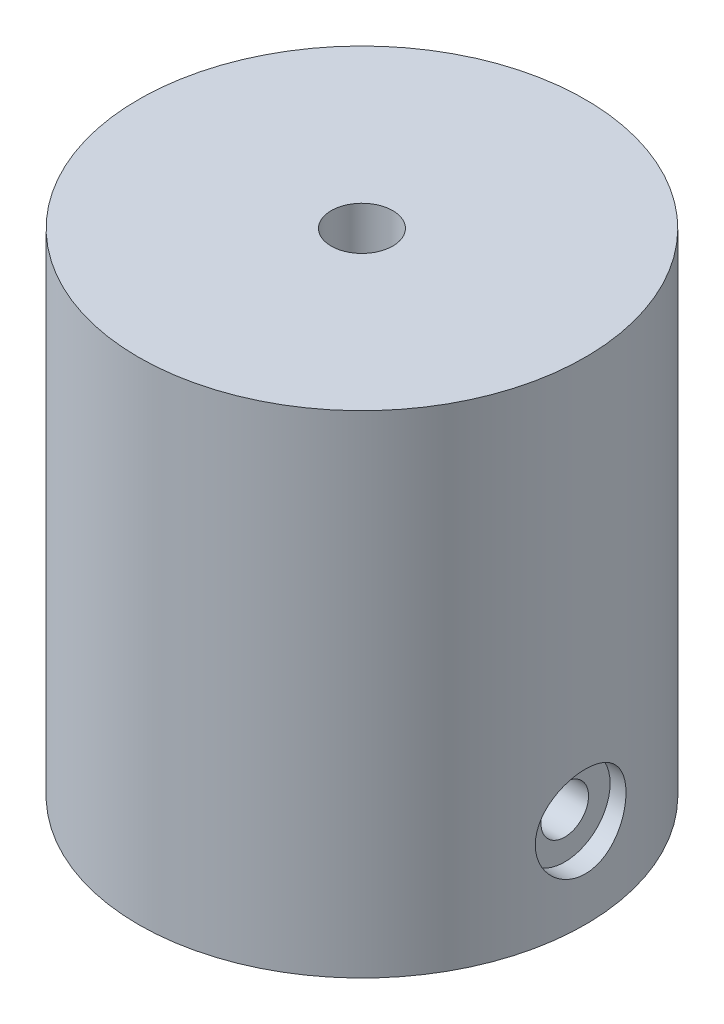
SolidWorks part; units mm, degrees
ref_plane "Front Plane" through (0, 0, 0) normal (0, 0, 1) x (1, 0, 0)
ref_plane "Top Plane" through (0, 0, 0) normal (0, 1, 0) x (1, 0, 0)
ref_plane "Right Plane" through (0, 0, 0) normal (1, 0, 0) x (0, 0, -1)
sketch "Sketch1" plane through (0, 0, 0) normal (0, 1, 0) x (1, 0, 0)
  circle A0 centre (0, 0) radius 12.7
  dimension "D1" = 25.4
extrude "Boss-Extrude1" add sketch "Sketch1" along normal blind 27.94
hole_wizard "Ø3.0mm Dowel Hole2" positions "Sketch2" profile "Sketch3" hole size "Ø3.0" standard "ANSI Metric" end condition through all
sketch "Sketch2" plane through (0, 27.94, 0) normal (0, 1, 0) x (1, 0, 0)
  point P0 (0, 0)
sketch "Sketch3" plane through (0, 27.94, 0) normal (1, 0, 0) x (0, 0, 1)
  line L0 (0, 0) -> (0, 27.94)
  line L1 (0, 27.94) -> (1.75, 27.94)
  line L2 (1.75, 27.94) -> (1.75, 0)
  line L5 (1.75, 0) -> (0, 0)
  line L11 (0, -6.35) -> (0, 107.95) construction
  dimension "Thru Hole Dia." = 3.5
  dimension "Thru Hole Depth" = 27.94
sketch "Sketch4" plane through (0, 0, 0) normal (1, 0, 0) x (0, 0, -1)
  line L0 (-12.7, 27.94) -> (-12.7, 0) construction
  line L1 (-12.7, 24.765) -> (-8.89, 24.765)
  line L2 (-12.7, 24.765) -> (-12.7, 3.175)
  line L3 (-12.7, 3.175) -> (-8.89, 3.175)
  line L4 (-8.89, 24.765) -> (-8.89, 3.175)
  line L5 (-12.7, 0) -> (12.7, 0) construction
  line L6 (12.7, 27.94) -> (-12.7, 27.94) construction
  line L7 (0, 0) -> (0, 26.8631) construction
  dimension "D1" = 3.175
  dimension "D2" = 3.175
  dimension "D3" = 3.81
ref_plane "Plane1" through (12.7, 0, 0) normal (1, 0, 0) x (0, 0, -1)
sketch "Sketch5" plane through (12.7, 0, 0) normal (1, 0, 0) x (0, 0, -1)
  line L0 (1.75, 27.94) -> (-1.75, 27.94) construction
  circle A0 centre (0, 22.86) radius 1.27
  circle A1 centre (0, 5.08) radius 1.27
  dimension "D3" = 2.54
  dimension "D1" = 5.08
  dimension "D2" = 5.08
hole_wizard "CBORE for #2 Button Head Cap Screw1" positions "Sketch6" profile "Sketch7" counterbore size "#2" standard "ANSI Inch" end condition up to next
sketch "Sketch6" plane through (12.7, 0, 0) normal (1, 0, 0) x (0, 0, -1)
  point P3 (0, 5.08)
sketch "Sketch7" plane through (12.7, 5.08, 0) normal (0, 1, 0) x (0, 0, -1)
  line L0 (0, 0) -> (0, 10.95)
  line L1 (0, 10.95) -> (1.3525, 10.95)
  line L3 (1.3525, 10.95) -> (1.3526, 1.1684)
  line L4 (1.3526, 1.1684) -> (2.5794, 1.1684)
  line L5 (2.5794, 1.1684) -> (2.5794, 0)
  line L7 (2.5794, 0) -> (0, 0)
  line L11 (0, -6.35) -> (0, 107.95) construction
  dimension "Thru Hole Dia." = 2.7051
  dimension "Thru Hole Depth" = 10.95
  dimension "C'Bore Dia." = 5.1587
  dimension "C'Bore Depth" = 1.1684
sketch "Sketch8" plane through (0, 0, 0) normal (0, -1, 0) x (1, 0, 0)
  circle A0 centre (0, 0) radius 2.75
  circle A1 centre (0, 0) radius 11.2
  circle A2 centre (0, 0) radius 1.75 construction
  circle A3 centre (0, 0) radius 12.7 construction
  dimension "D1" = 1
  dimension "D2" = 1.5
extrude "Cut-Extrude1" cut sketch "Sketch8" against normal blind 2.54
